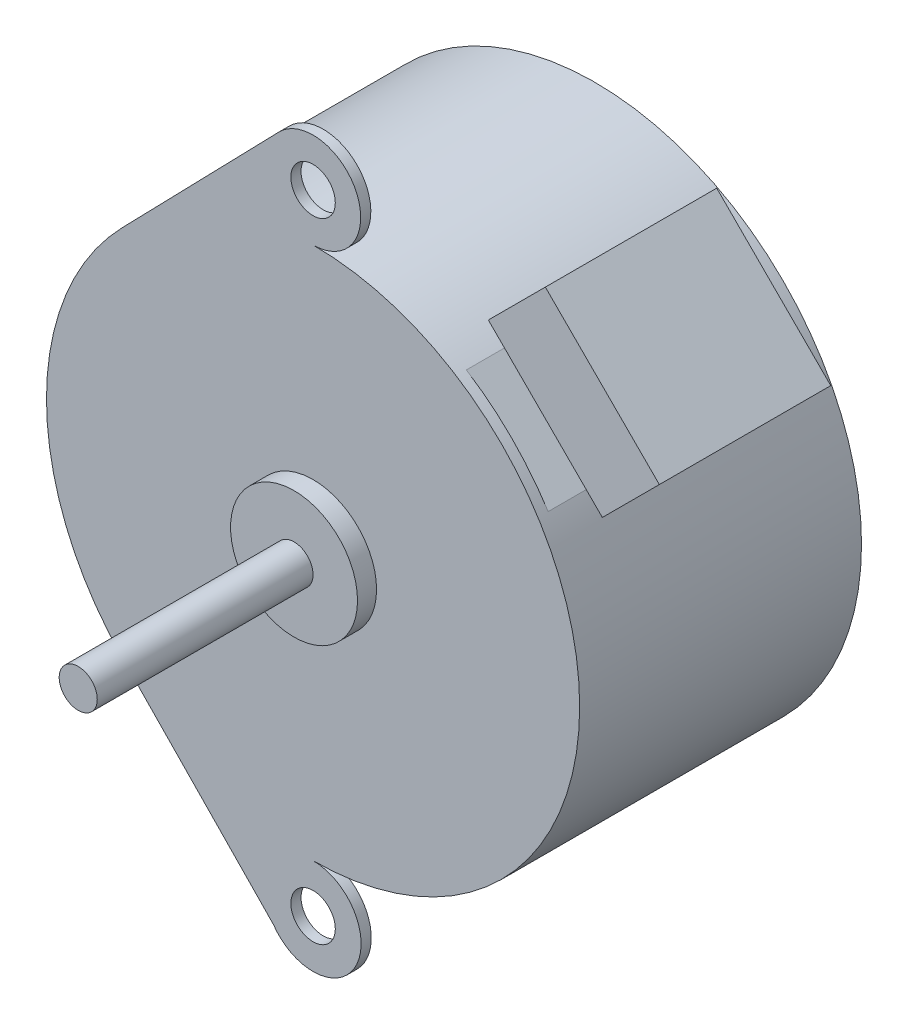
SolidWorks part; units mm, degrees
ref_plane "Front Plane" through (0, 0, 0) normal (0, 0, 1) x (1, 0, 0)
ref_plane "Top Plane" through (0, 0, 0) normal (0, 1, 0) x (1, 0, 0)
ref_plane "Right Plane" through (0, 0, 0) normal (1, 0, 0) x (0, 0, -1)
sketch "Sketch1" plane through (0, 0, 0) normal (0, 0, 1) x (1, 0, 0)
  circle A0 centre (0, 0) radius 21
extrude "Boss-Extrude1" add sketch "Sketch1" along normal blind 0.8
sketch "Sketch2" plane through (0, 0, 0) normal (0, 0, 1) x (1, 0, 0)
  line L0 (0, 33.3138) -> (0, -50.5841) construction
  line L1 (0, 0) -> (-21, 0) construction
  line L2 (-15.0591, -14.6364) -> (-3.122, -26.9183)
  line L3 (-15.0591, 14.6364) -> (-2.6923, 27.3604)
  arc A0 (0, 21) -> (-2.6923, 27.3604) centre (0, 24.75) ccw
  arc A1 (-3.122, -26.9183) -> (0, -21) centre (0, -24.7826) ccw
  circle A2 centre (0, 0) radius 21 construction
  circle A3 centre (0, 24.75) radius 1.75
  circle A4 centre (0, -24.7826) radius 1.75
  arc A5 (-15.0591, 14.6364) -> (-15.0591, -14.6364) centre (0, 0) ccw
  arc A6 (0, -21) -> (0, 21) centre (0, 0) ccw
  point P1 (0, 0)
  point P16 (0, 0)
  point P18 (0, 0)
  point P19 (0, 0)
  point P20 (0, 0)
  point P21 (0, 0)
  point P22 (0, 0)
  point P23 (0, 0)
  point P24 (0, 0)
  point P25 (0, 0)
  point P26 (0, 0)
  point P27 (0, 0)
  point P28 (-29.3406, 0)
  point P29 (-29.3406, 0)
  point P30 (-29.2846, 0)
  dimension "D1" = 3.5
  dimension "D2" = 7.5
extrude "Boss-Extrude2" add sketch "Sketch2" along normal blind 0.8
sketch "Sketch5" plane through (0, 0, 0) normal (0, 0, 1) x (1, 0, 0)
  circle A0 centre (0, 0) radius 21
extrude "Boss-Extrude4" add sketch "Sketch5" against normal blind 21.4
sketch "Sketch6" plane through (0, 0, 0) normal (0, 0, 1) x (1, 0, 0)
  circle A0 centre (0, 0) radius 4
extrude "Boss-Extrude5" add sketch "Sketch6" against normal blind 22.4
sketch "Sketch7" plane through (0, 0, 0) normal (0, 0, 1) x (1, 0, 0)
  circle A0 centre (0, 0) radius 5
extrude "Boss-Extrude6" add sketch "Sketch7" along normal blind 2.3
sketch "Sketch8" plane through (0, 0, 0) normal (0, 0, 1) x (1, 0, 0)
  circle A0 centre (0, 0) radius 1.5
extrude "Boss-Extrude7" add sketch "Sketch8" along normal blind 19.3
sketch "Sketch9" plane through (0, 0, 0) normal (0, 0, 1) x (1, 0, 0)
  line L0 (18.9858, 10.0056) -> (10.0056, 18.9858)
  line L1 (10.0056, 18.9858) -> (14.4957, 23.4759)
  line L2 (14.4957, 23.4759) -> (23.4759, 14.4957)
  line L3 (23.4759, 14.4957) -> (18.9858, 10.0056)
extrude "Boss-Extrude8" add sketch "Sketch9" against normal blind 16.5
sketch "Sketch10" plane through (0, 0, 0) normal (0, 0, 1) x (1, 0, 0)
  line L0 (10.0056, 18.9858) -> (18.9858, 10.0056)
  line L1 (10.0056, 18.9858) -> (14.5725, 23.5527)
  line L2 (18.9858, 10.0056) -> (23.5527, 14.5725)
  line L3 (14.5725, 23.5527) -> (23.5527, 14.5725)
extrude "Cut-Extrude1" cut sketch "Sketch10" against normal blind 3
